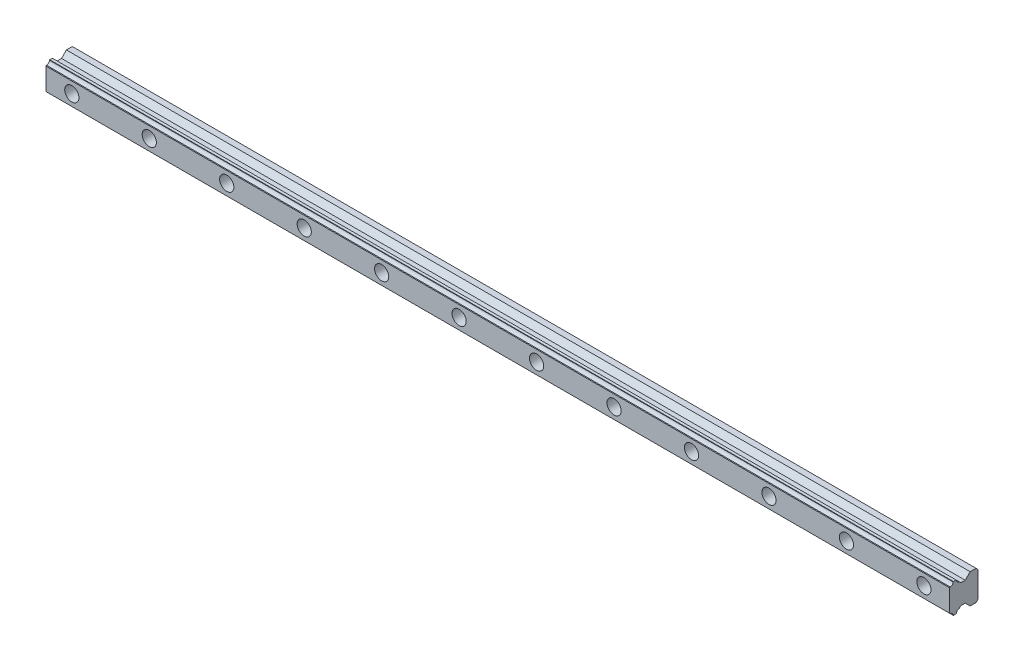
SolidWorks part; units mm, degrees
material "AISI 1035 鋼 (SS)"
ref_plane "Front Plane" through (0, 0, 0) normal (0, 0, 1) x (1, 0, 0)
ref_plane "Top Plane" through (0, 0, 0) normal (0, 1, 0) x (1, 0, 0)
ref_plane "Right Plane" through (0, 0, 0) normal (1, 0, 0) x (0, 0, -1)
ref_plane "Plane1" through (-20, 0, 0) normal (-1, 0, 0) x (0, -1, 0)
sketch "Sketch1" plane through (-20, 0, 0) normal (-1, 0, 0) x (0, -1, 0)
  line L0 (-7.7, 0) -> (7.7, 0)
  line L1 (7.7, 0) -> (7.7, 13.2801)
  line L2 (7.7, 13.2801) -> (8.9297, 14.5098)
  line L3 (11.4, 16.7868) -> (11.4, 21.9)
  line L4 (11.4, 21.9) -> (-11.4, 21.9)
  line L5 (-11.4, 21.9) -> (-11.4, 16.7868)
  line L6 (-8.9297, 14.5098) -> (-7.7, 13.2801)
  line L7 (-7.7, 13.2801) -> (-7.7, 0)
  arc A0 (8.9297, 14.5098) -> (11.4, 16.7868) centre (11.4471, 14.2573) cw
  arc A1 (-11.4, 16.7868) -> (-8.9297, 14.5098) centre (-11.4471, 14.2573) cw
extrude "Boss-Extrude1" add sketch "Sketch1" against normal blind 700
sketch "Sketch2" plane through (0, -7.7, 0) normal (0, -1, 0) x (1, 0, 0)
  line L0 (680, 9.8986) -> (680, 0)
  line L1 (680, 0) -> (-20, 0)
  line L2 (-20, 0) -> (-20, 9.8986)
  line L3 (-20, 9.8986) -> (680, 9.8986)
extrude "Boss-Extrude2" add sketch "Sketch2" along normal blind 3.8
sketch "Sketch3" plane through (0, 7.7, 0) normal (0, 1, 0) x (-1, 0, 0)
  line L0 (-680, 0) -> (-680, 6.0986)
  line L1 (-680, 6.0986) -> (20, 6.0986)
  line L2 (20, 6.0986) -> (20, 0)
  line L3 (20, 0) -> (-680, 0)
extrude "Boss-Extrude3" add sketch "Sketch3" along normal blind 3.8
sketch "Sketch4" plane through (680, 0, 0) normal (1, 0, 0) x (0, 0, -1)
  line L0 (-21.9, -11.4) -> (-19.2129, -11.4)
  line L1 (-21.9, -8.922) -> (-21.9, -11.4)
  arc A0 (-19.2129, -11.4) -> (-21.9, -8.922) centre (-21.7425, -11.4471) ccw
extrude "Cut-Extrude1" cut sketch "Sketch4" against normal through all
sketch "Sketch5" plane through (680, 0, 0) normal (1, 0, 0) x (0, 0, -1)
  line L0 (-21.9, 11.4) -> (-21.9, 8.922)
  line L1 (-19.2129, 11.4) -> (-21.9, 11.4)
  arc A0 (-21.9, 8.922) -> (-19.2129, 11.4) centre (-21.7425, 11.4471) ccw
extrude "Cut-Extrude2" cut sketch "Sketch5" against normal through all
draft "Draft1" type of draft neutral plane draft angle 45 faces to draft 1 face at (330, 9.6, 6.0986) neutral plane through (0, 11.5, 0) neutral plane normal (0, 1, 0) parameters "D1"=45
draft "Draft2" type of draft neutral plane draft angle 45 faces to draft 1 face at (330, -9.6, 9.8986) neutral plane through (680, -7.7, 0) neutral plane normal (0, -1, 0) parameters "D1"=45
hole_wizard "CBORE for M6 Hex Head Bolt1" positions "Sketch7" profile "Sketch6" counterbore size "M6" standard "ANSI Metric"
sketch "Sketch7" plane through (0, 0, 21.9) normal (0, 0, 1) x (1, 0, 0)
  point P0 (60, 0)
  point P1 (120, 0)
  point P2 (180, 0)
  point P3 (240, 0)
  point P4 (300, 0)
  point P5 (360, 0)
  point P6 (420, 0)
  point P7 (480, 0)
  point P8 (540, 0)
  point P9 (600, 0)
  point P10 (660, 0)
  point P11 (0, 0)
sketch "Sketch6" plane through (60, 0, 21.9) normal (1, 0, 0) x (0, -1, 0)
  line L0 (0, 0) -> (0, 21.9)
  line L1 (0, 21.9) -> (3.5, 21.9)
  line L3 (3.5, 21.9) -> (3.5, 8.9)
  line L4 (3.5, 8.9) -> (5.5, 8.9)
  line L5 (5.5, 8.9) -> (5.5, 0)
  line L7 (5.5, 0) -> (0, 0)
  line L11 (0, -6.35) -> (0, 107.95) construction
  dimension "Thru Hole Dia." = 7
  dimension "Thru Hole Depth" = 21.9
  dimension "C'Bore Dia." = 11
  dimension "C'Bore Depth" = 8.9
chamfer "Chamfer1" distance 0.1849 angle 45 4 edges at (330, -11.4, 19.2129) (330, 11.4, 19.2129) (330, -11.4, 16.7868) (330, 11.4, 16.7868) first distance on face at (330, -9.8741, 20.2919) first distance on face at (330, 11.4, 17.9999) first distance on face at (330, -9.9486, 15.883)
chamfer "Chamfer2" distance 0.3778 angle 45 2 edges at (330, 8.922, 21.9) (330, -8.922, 21.9) first distance on face at (330, 9.7925, 20.3315) first distance on face at (65.5, 0, 21.9)
chamfer "Chamfer3" distance 1.5 angle 45 2 edges at (330, -11.5, 0) (330, 11.5, 0)
